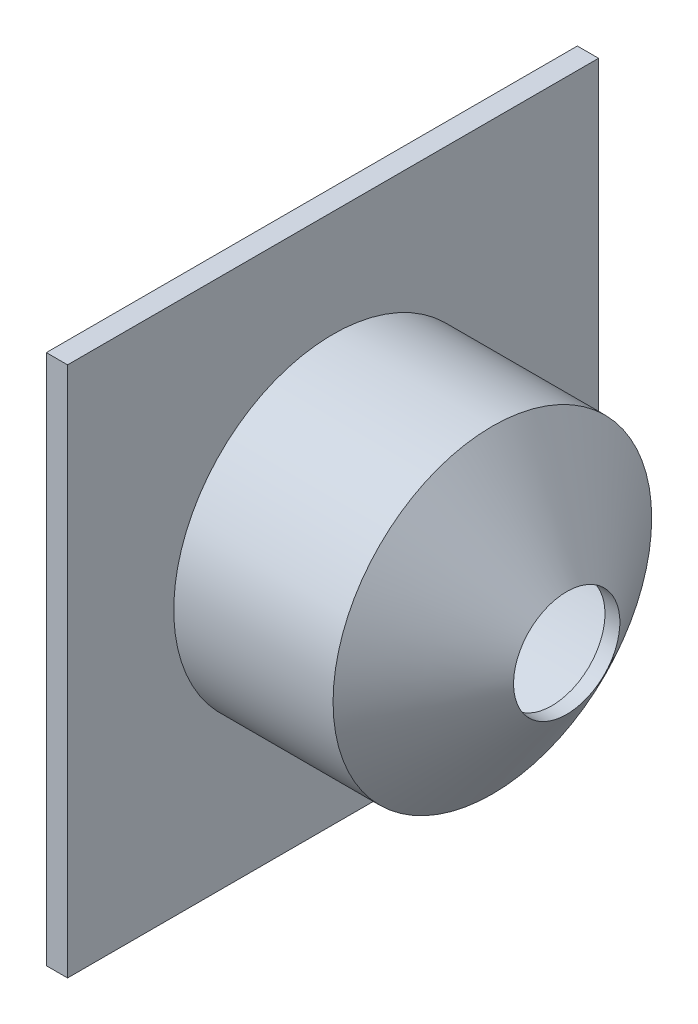
SolidWorks part; units mm, degrees
ref_plane "Front Plane" through (0, 0, 0) normal (0, 0, 1) x (1, 0, 0)
ref_plane "Top Plane" through (0, 0, 0) normal (0, 1, 0) x (1, 0, 0)
ref_plane "Right Plane" through (0, 0, 0) normal (1, 0, 0) x (0, 0, -1)
sketch "Sketch1" plane through (0, 0, 0) normal (1, 0, 0) x (0, 0, -1)
  line L1 (-25, 25) -> (25, 25)
  line L2 (-25, 25) -> (-25, -25)
  line L3 (-25, -25) -> (25, -25)
  line L4 (25, 25) -> (25, -25)
  line L5 (-25, 25) -> (25, -25) construction
  line L6 (-25, -25) -> (25, 25) construction
  circle A0 centre (0, 0) radius 15
  circle A1 centre (0, 0) radius 13
  point P2 (0, 0)
  dimension "D1" = 50
  dimension "D3" = 30
  dimension "D2" = 50
extrude "Boss-Extrude1" add sketch "Sketch1" along normal blind 17 contours A0 A1 region at (0, 0, 14.5757)
extrude "Boss-Extrude2" add sketch "Sketch1<4>" along normal blind 2 separate body contours L4 L1 L2 L3 A0 region at (0, 24.2929, 0)
sketch "Sketch1<4>" plane through (0, 0, 0) normal (1, 0, 0) x (0, 0, -1) same geometry as "Sketch1"
sketch "Sketch5" plane through (0, 0, 0) normal (0, 1, 0) x (1, 0, 0)
  line L0 (17, 15) -> (23.9976, 5.0063)
  line L1 (17, 13) -> (22.5972, 5.0063)
  line L2 (22.5972, 5.0063) -> (23.9976, 5.0063)
  line L3 (17, 13) -> (17, 15)
  line L4 (-1.322, 0) -> (30.7907, 0)
revolve "Revolve1" add sketch "Sketch5" angle 360 about L4
